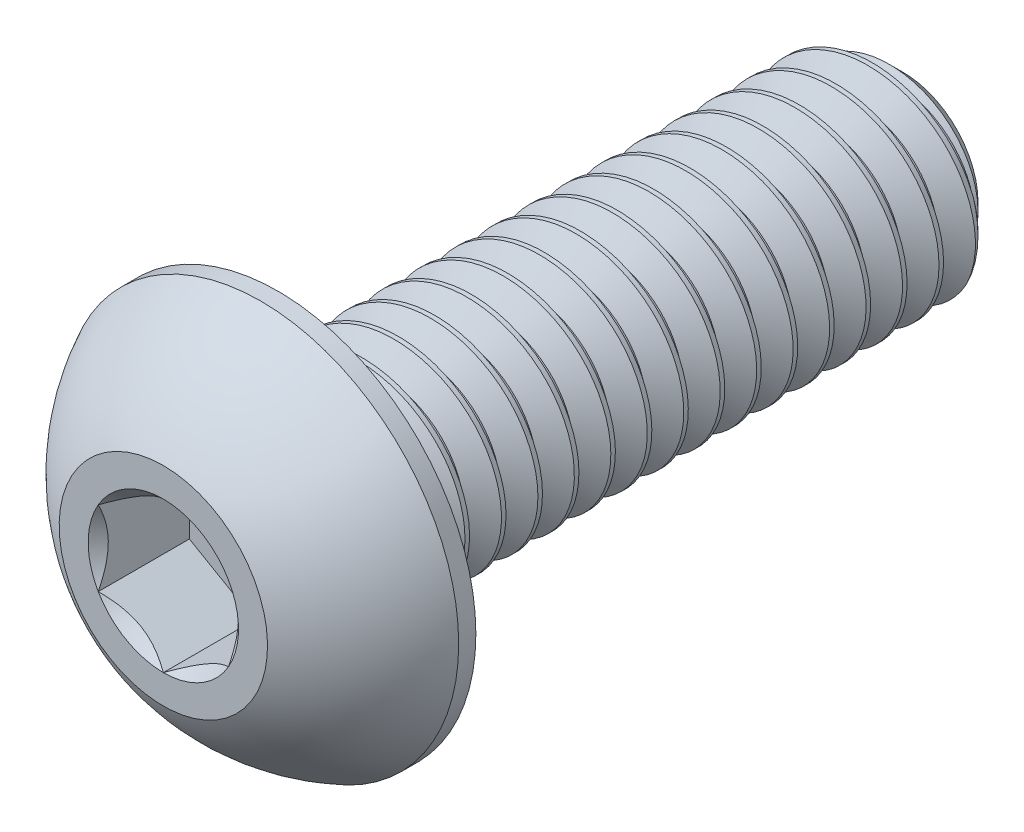
SolidWorks part; units mm, degrees
ref_plane "Front Plane" through (0, 0, 0) normal (0, 0, 1) x (1, 0, 0)
ref_plane "Top Plane" through (0, 0, 0) normal (0, 1, 0) x (1, 0, 0)
ref_plane "Right Plane" through (0, 0, 0) normal (1, 0, 0) x (0, 0, -1)
sketch "Sketch1" plane through (0, 0, 0) normal (1, 0, 0) x (0, 0, -1)
  line L0 (-7.1, 0) -> (7.1, 0) construction
  line L1 (-4.9, 3.8) -> (-4.9, -3.8) construction
  line L2 (7.1, 2) -> (7.1, -2) construction
  line L3 (7.0563, 2.0758) -> (7.4063, 1.4696) construction
  line L4 (7.4063, 1.4696) -> (7.7563, 2.0758) construction
  line L5 (7.7563, 2.0758) -> (7.0563, 2.0758) construction
  line L6 (7.1, 2) -> (7.7125, 2) construction
  line L7 (7.4063, 2.0758) -> (7.4063, 2) construction
  line L8 (7.4063, 2) -> (7.4063, 1.5453) construction
  line L9 (7.4063, 1.5453) -> (7.4063, 1.4696) construction
  line L10 (7.3625, 1.5453) -> (7.45, 1.5453)
  line L11 (7.0781, 2.0379) -> (7.7344, 2.0379)
  line L12 (7.45, 1.5453) -> (7.7344, 2.0379)
  line L13 (7.3625, 1.5453) -> (7.0781, 2.0379)
  line L14 (-7.1, 1.25) -> (-7.1, -1.25) construction
  line L15 (7.1, 2) -> (-4.9, 2) construction
  point P3 (-4.9, 0)
  point P6 (-5.35, 0)
  point P21 (7.4063, 2.0379)
  point P24 (-5.23, 3.8)
  point P25 (5.35, -2)
  point P26 (-7.1, 2)
  dimension "Head Height" = 2.2
  dimension "Length" = 12
  dimension "Head Dia" = 7.6
  dimension "Thread Dia" = 4
  dimension "Pitch" = 0.7
  dimension "Drive Size" = 2.5
  dimension "D1" = 1.75
  dimension "D3" = 0.33
  dimension "D4" = 1.75
sketch "Sketch2" plane through (0, 0, 0) normal (1, 0, 0) x (0, 0, -1)
  line L0 (-7.1, 0) -> (7.1, 0)
  line L1 (7.1, 0) -> (7.1, 1.44)
  line L2 (7.1, 2) -> (7.1, -2) construction
  line L3 (7.1, 1.44) -> (6.54, 2)
  line L4 (6.54, 2) -> (-4.9, 2)
  line L5 (-4.9, 3.8) -> (-4.9, -3.8) construction
  line L6 (-4.9, 2) -> (-4.9, 3.8)
  line L7 (-4.9, 3.8) -> (-5.23, 3.8)
  line L8 (7.1, 2) -> (7.7125, 2) construction
  line L9 (-7.1, 0) -> (-7.1, 2)
  arc A0 (-7.1, 2) -> (-5.23, 3.8) centre (-3.3736, 0) cw
  dimension "D1" = 0.56
  dimension "D2" = 45
revolve "Revolve1" add sketch "Sketch2" angle 360 about L0
sketch "Sketch3" plane through (0, 0, 7.1) normal (0, 0, 1) x (1, 0, 0)
  line L1 (0, 1.4434) -> (-1.25, 0.7217)
  line L2 (-1.25, 0.7217) -> (-1.25, -0.7217)
  line L3 (-1.25, -0.7217) -> (0, -1.4434)
  line L4 (0, -1.4434) -> (1.25, -0.7217)
  line L5 (1.25, -0.7217) -> (1.25, 0.7217)
  line L6 (1.25, 0.7217) -> (0, 1.4434)
  circle A0 centre (0, 0) radius 1.25 construction
  dimension "D1" = 2.5
extrude "Cut-Extrude1" cut sketch "Sketch3" against normal up to vertex (1.75 mm away) up to point (0, 0, 5.35)
sketch "Sketch4" plane through (0, 0, 7.1) normal (0, 0, 1) x (1, 0, 0)
  circle A0 centre (0, 0) radius 1.4434
extrude "Cut-Extrude2" cut sketch "Sketch4" against normal blind 10 draft 45
split "Split1" bodies to split 106 resulting bodies 107 108 split by face at (3.8, 0, 4.9)
sketch "Sketch5" plane through (0, 0, -7.1) normal (0, 0, -1) x (-1, 0, 0)
  circle A0 centre (0, 0) radius 2 construction
  circle A1 centre (0, 0) radius 2
curve "Helix/Spiral1" pitch 0.7 height 12.7 radius 2 centre (0, 0, -7.1) axis (0, 0, 1) start towards (0, 1, 0)
sketch "Sketch6" plane through (0, 0, 0) normal (1, 0, 0) x (0, 0, -1)
  line L0 (7.3625, 1.5453) -> (7.45, 1.5453) construction
  line L1 (7.3625, 1.5453) -> (7.0781, 2.0379) construction
  line L2 (7.0781, 2.0379) -> (7.7344, 2.0379) construction
  line L3 (7.45, 1.5453) -> (7.7344, 2.0379) construction
  line L4 (7.3625, 1.5453) -> (7.45, 1.5453)
  line L5 (7.3625, 1.5453) -> (7.0781, 2.0379)
  line L6 (7.0781, 2.0379) -> (7.7344, 2.0379)
  line L7 (7.45, 1.5453) -> (7.7344, 2.0379)
sweep "Cut-Sweep1" cut profiles "Sketch6" path "Helix/Spiral1" align with end faces yes
sketch "Sketch7" plane through (0, 0, 4.9) normal (0, 0, -1) x (-1, 0, 0)
  circle A1 centre (0, 0) radius 2
  circle A2 centre (0, 0) radius 2
  dimension "D1" = 0
extrude "Boss-Extrude1" add sketch "Sketch7" along normal blind 10 draft 30
equation "\"D2@Sketch1\" = \"Pitch@Sketch1\" / 8"
equation "\"D1@Sketch1\"=\"Drive Size@Sketch1\"*.7"
equation "\"D3@Sketch1\"=\"Head Height@Sketch1\"*.15"
equation "\"D1@Sketch2\"=\"Pitch@Sketch1\"*.8"
equation "\"D1@Sketch3\"=\"Drive Size@Sketch1\""
equation "\"D4@Helix/Spiral1\"=\"Pitch@Sketch1\""
equation "\"D3@Helix/Spiral1\"=\"Length@Sketch1\"+\"Pitch@Sketch1\""
equation "\"D4@Sketch1\"=\"Pitch@Sketch1\"*2.5"
